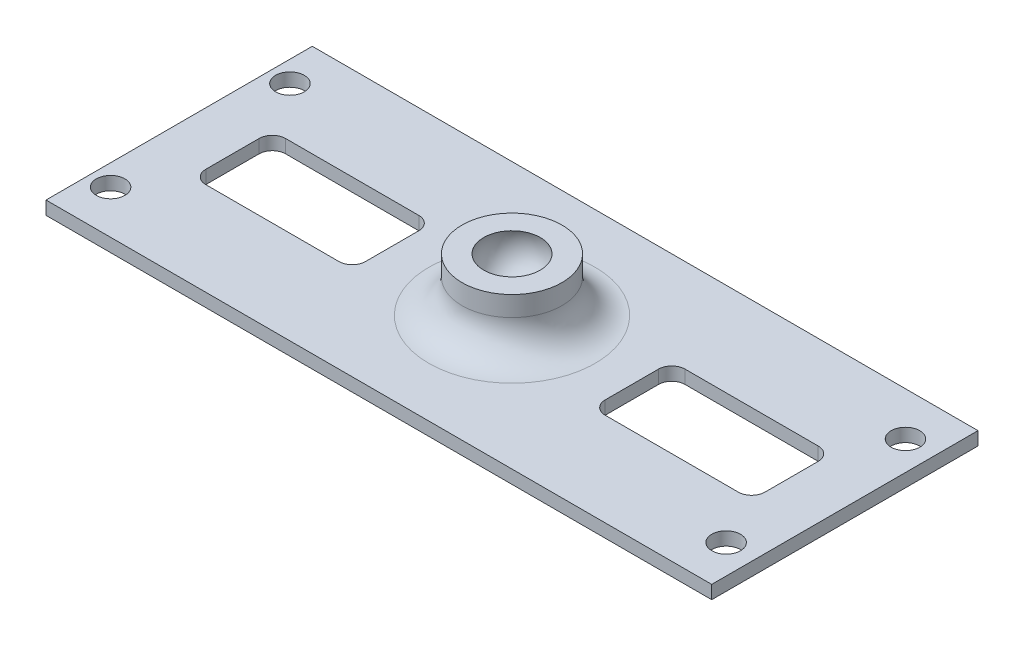
SolidWorks part; units mm, degrees
material "ABS"
ref_plane "Front Plane" through (0, 0, 0) normal (0, 0, 1) x (1, 0, 0)
ref_plane "Top Plane" through (0, 0, 0) normal (0, 1, 0) x (1, 0, 0)
ref_plane "Right Plane" through (0, 0, 0) normal (1, 0, 0) x (0, 0, -1)
sketch "Sketch1" plane through (0, 0, 0) normal (0, 1, 0) x (1, 0, 0)
  line L1 (-50, 20) -> (50, 20)
  line L2 (-50, 20) -> (-50, -20)
  line L3 (-50, -20) -> (50, -20)
  line L4 (50, 20) -> (50, -20)
  line L5 (-50, 20) -> (50, -20) construction
  line L6 (-50, -20) -> (50, 20) construction
  point P0 (0, 0)
  dimension "D1" = 40
  dimension "D2" = 100
extrude "Boss-Extrude1" add sketch "Sketch1" along normal blind 2
hole_wizard "#6 Clearance Hole1" positions "Sketch2" profile "Sketch3" hole size "#6" standard "ANSI Inch" end condition through all
sketch "Sketch2" plane through (0, 2, 0) normal (0, 1, 0) x (1, 0, 0)
  arc A0 (45.6352, 12.1178) -> (45.6352, 14.8229) centre (45.6352, 13.4704) ccw construction
  arc A1 (45.6352, -14.8229) -> (45.6352, -12.1178) centre (45.6352, -13.4704) ccw construction
  arc A2 (-46.825, 14.8229) -> (-46.825, 12.1178) centre (-46.825, 13.4704) ccw construction
  arc A3 (-46.825, -12.1178) -> (-46.825, -14.8229) centre (-46.825, -13.4704) ccw construction
  point P0 (45.6352, 13.4704)
  point P2 (45.6352, -13.4704)
  point P4 (-46.825, -13.4704)
  point P6 (-46.825, 13.4704)
  point P29 (0, 0)
sketch "Sketch3" plane through (45.6352, 2, -13.4704) normal (1, 0, 0) x (0, 0, 1)
  line L0 (0, 0) -> (0, 2)
  line L1 (0, 2) -> (2.1526, 2)
  line L2 (2.1526, 2) -> (2.1526, 0)
  line L5 (2.1526, 0) -> (0, 0)
  line L11 (0, -6.35) -> (0, 107.95) construction
  dimension "Thru Hole Dia." = 4.3053
  dimension "Thru Hole Depth" = 2
sketch "Esquisse1" plane through (0, 2, 0) normal (0, 1, 0) x (1, 0, 0)
  circle A0 centre (0, 0) radius 7.5
  dimension "D1" = 15
extrude "Boss.-Extru.2" add sketch "Esquisse1" along normal blind 8
sketch "Esquisse3" plane through (0, 0, 0) normal (0, 0, 1) x (1, 0, 0)
  line L1 (7.5, 10) -> (-7.5, 10) construction
  line L2 (0, 0) -> (0, 15.9939) construction
  line L3 (0, 3.7) -> (0, 12.8671)
  arc A0 (0, 12.8671) -> (0, 3.7) centre (0, 8.2835) ccw
  point P2 (4.25, 10)
  point P3 (-4.25, 10)
  point P5 (0, 3.7)
  dimension "D1" = 0
  dimension "D4" = 6.3
  dimension "D2" = 8.5
  dimension "D3" = 0
  dimension "D5" = 0
revolve "Enlèvement de matière-Révolution1" cut sketch "Esquisse3" angle 360 about L2
fillet "Congé1" radius 5 1 edges at (0, 2, 7.5)
sketch "Esquisse5" plane through (0, 2, 0) normal (0, 1, 0) x (1, 0, 0)
  line L0 (-50, -20) -> (50, -20) construction
  line L1 (-40, -6) -> (-20, -6)
  line L2 (-42, -4) -> (-42, 4)
  line L3 (-40, 6) -> (-20, 6)
  line L4 (-18, -4) -> (-18, 4)
  line L5 (-42, -6) -> (-18, 6) construction
  line L6 (-42, 6) -> (-18, -6) construction
  arc A0 (-20, 6) -> (-18, 4) centre (-20, 4) cw
  arc A1 (-20, -6) -> (-18, -4) centre (-20, -4) ccw
  arc A2 (-40, -6) -> (-42, -4) centre (-40, -4) cw
  arc A3 (-42, 4) -> (-40, 6) centre (-40, 4) cw
  point P0 (-30, 0)
  point P5 (0, 0)
  dimension "D5" = 2
  dimension "D1" = 12
  dimension "D2" = 24
  dimension "D3" = 30
  dimension "D4" = 20
extrude "Enlèv. mat.-Extru.1" cut sketch "Esquisse5" against normal blind 8
mirror "Symétrie1" about plane through (0, 0, 0) normal (1, 0, 0) of "Enlèv. mat.-Extru.1"
equation "\"1é5\"=2"
